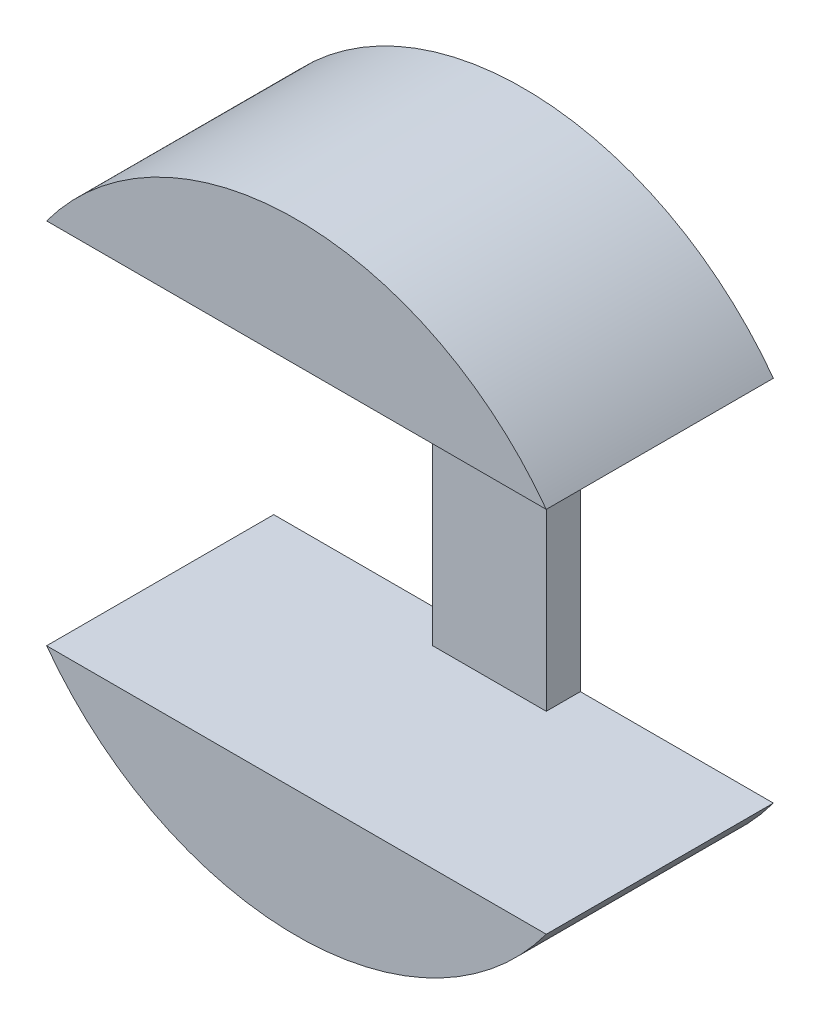
SolidWorks part; units mm, degrees
material "ABS"
ref_plane "Спереди" through (0, 0, 0) normal (0, 0, 1) x (1, 0, 0)
ref_plane "Сверху" through (0, 0, 0) normal (0, 1, 0) x (1, 0, 0)
ref_plane "Справа" through (0, 0, 0) normal (1, 0, 0) x (0, 0, -1)
ref_axis "Ось1" through (0, 0, 50) along (0, 0, -1)
sketch "Эскиз2" plane through (0, 0, 0) normal (0, 0, 1) x (1, 0, 0)
  line L0 (-2.5, 8.1) -> (-11, 8.1)
  line L1 (-2.5, -8.1) -> (2.5, -8.1) construction
  line L2 (-2.5, -8.1) -> (-2.5, 8.1)
  line L3 (-2.5, 8.1) -> (2.5, 8.1) construction
  line L4 (2.5, -8.1) -> (2.5, 8.1)
  line L5 (-2.5, -8.1) -> (2.5, 8.1) construction
  line L6 (-2.5, 8.1) -> (2.5, -8.1) construction
  line L7 (2.5, 8.1) -> (11, 8.1)
  line L8 (-2.5, -8.1) -> (-11, -8.1)
  line L9 (2.5, -8.1) -> (11, -8.1)
  arc A0 (-11, 8.1) -> (11, 8.1) centre (0, 0) cw
  arc A1 (11, -8.1) -> (-11, -8.1) centre (0, 0) cw
  point P6 (11, -8.2)
  point P11 (-10.8301, -8.2)
  point P12 (-11, -8.2)
  dimension "D2" = 5
  dimension "D3" = 16.2
  dimension "D4" = 22
extrude "Бобышка-Вытянуть1" add sketch "Эскиз2" along normal blind 10
sketch "Эскиз3" plane through (0, 0, 10) normal (0, 0, 1) x (1, 0, 0)
  line L0 (2.5, -8.1) -> (2.5, 8.1) construction
  line L1 (2.5, -8.1) -> (-2.5, -8.1)
  line L2 (2.5, -8.1) -> (2.5, 8.1)
  line L3 (2.5, 8.1) -> (-2.5, 8.1)
  line L4 (-2.5, -8.1) -> (-2.5, 8.1)
  line L5 (11, -8.1) -> (2.5, -8.1) construction
  line L6 (2.5, 8.1) -> (11, 8.1) construction
  point P0 (0, 0)
  point P5 (2.5, 8.2)
  point P6 (-2.5, 8.2)
  point P8 (2.5, -8.2)
  point P11 (-2.5, -8.2)
  point P12 (2.5, -8.1)
  point P16 (-2.5, -8.1)
  point P17 (-2.5, -8.1)
  point P18 (-2.5, -8.1)
  point P20 (2.5, -8.1)
extrude "Вырез-Вытянуть1" cut sketch "Эскиз3" against normal offset from surface (8.5 mm away) 1.5 up to face at (0, 0, 0)
